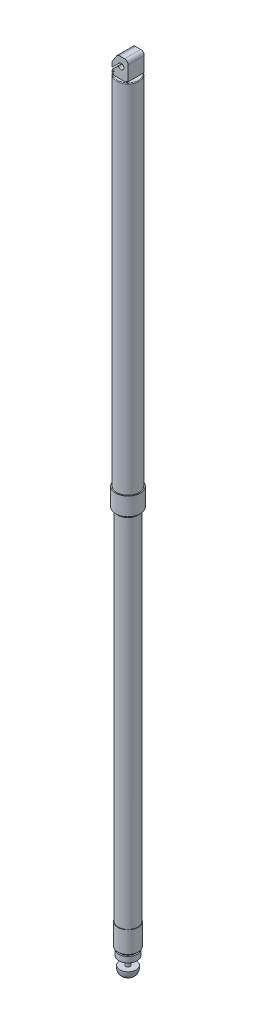
SolidWorks part; units mm, degrees
ref_plane "Front Plane" through (0, 0, 0) normal (0, 0, 1) x (1, 0, 0)
ref_plane "Top Plane" through (0, 0, 0) normal (0, 1, 0) x (1, 0, 0)
ref_plane "Right Plane" through (0, 0, 0) normal (1, 0, 0) x (0, 0, -1)
sketch "Sketch1" plane through (0, 0, 0) normal (0, 0, 1) x (1, 0, 0)
  line L0 (-33.0085, -30.177) -> (-48.0085, -30.177)
  line L1 (-48.0085, -30.177) -> (-56.0085, -42.8656)
  line L2 (-56.0085, -42.8656) -> (-56.0085, -49.4403)
  line L3 (-56.0085, -49.4403) -> (-46.7672, -40.8087)
  line L5 (-46.7672, -43.5454) -> (-56.0085, -52.177)
  line L6 (-56.0085, -52.177) -> (-53.0085, -52.177)
  line L7 (-53.0085, -52.177) -> (-53.0085, -54.177)
  line L8 (-53.0085, -54.177) -> (-56.0085, -54.177)
  line L9 (-56.0085, -54.177) -> (-56.0085, -56.177)
  line L10 (-56.0085, -56.177) -> (-54.0085, -56.177)
  line L11 (-54.0085, -56.177) -> (-54.0085, -58.177)
  line L12 (-54.0085, -58.177) -> (-35.0085, -58.177)
  line L13 (-35.0085, -58.177) -> (-35.0085, -56.177)
  line L14 (-35.0085, -56.177) -> (-33.0085, -56.177)
  line L15 (-33.0085, -56.177) -> (-33.0085, -30.177)
  arc A0 (-46.7672, -43.5454) -> (-46.7672, -40.8087) centre (-43.0085, -42.177) ccw
  dimension "D15" = 4
  dimension "D2" = 28
  dimension "D3" = 2
  dimension "D4" = 2
  dimension "D5" = 2
  dimension "D6" = 2
  dimension "D7" = 2
  dimension "D8" = 15
  dimension "D9" = 15
  dimension "D10" = 2
  dimension "D11" = 3
  dimension "D12" = 19
  dimension "D13" = 12
  dimension "D14" = 10
extrude "Boss-Extrude1" add sketch "Sketch1" along normal mid plane 23
fillet "Fillet1" radius 5 3 edges at (-56.0085, -42.8656, 0) (-48.0085, -30.177, 0) (-33.0085, -30.177, 0)
sketch "Sketch2" plane through (0, -58.177, 0) normal (0, -1, 0) x (-1, 0, 0)
  line L0 (35.0085, -11.5) -> (54.0085, 11.2984) construction
  line L1 (54.0085, -11.5) -> (54.0085, 11.5) construction
  circle A0 centre (44.5085, -0.1008) radius 16
  dimension "D1" = 32
extrude "Boss-Extrude2" add sketch "Sketch2" along normal blind 508
fillet "Fillet2" radius 1 1 edges at (-44.5085, -58.177, -15.8992)
ref_axis "Axis1" through (-44.5085, -566.177, 0.1008) along (0, 1, 0)
sketch "Sketch4" plane through (0, -566.177, 0) normal (0, -1, 0) x (-1, 0, 0)
  circle A0 centre (44.5085, -0.1008) radius 17.5
  dimension "D1" = 35
extrude "Boss-Extrude3" add sketch "Sketch4" along normal blind 29
chamfer "Chamfer1" distance 3.5 angle 45 1 edges at (-44.5085, -595.177, -17.3992)
sketch "Sketch5" plane through (0, -595.177, 0) normal (0, -1, 0) x (-1, 0, 0)
  circle A1 centre (44.5085, -0.1008) radius 14
  circle A2 centre (44.5085, -0.1008) radius 14
  dimension "D1" = 0
extrude "Boss-Extrude4" add sketch "Sketch5" along normal blind 508
sketch "Sketch6" plane through (0, -1103.177, 0) normal (0, -1, 0) x (1, 0, 0)
  circle A0 centre (-44.5085, 0.1008) radius 14.5
  dimension "D1" = 29
extrude "Boss-Extrude5" add sketch "Sketch6" along normal blind 34
chamfer "Chamfer2" distance 3.5 angle 45 1 edges at (-44.5085, -1137.177, -14.3992)
sketch "Sketch7" plane through (0, -1137.177, 0) normal (0, -1, 0) x (1, 0, 0)
  circle A0 centre (-44.5085, 0.1008) radius 13
  circle A1 centre (-44.5085, 0.1008) radius 11 construction
  dimension "D1" = 26
extrude "Boss-Extrude6" add sketch "Sketch7" along normal blind 8
sketch "Sketch8" plane through (0, -1145.177, 0) normal (0, -1, 0) x (1, 0, 0)
  circle A0 centre (-44.5085, 0.1008) radius 3.175
  circle A2 centre (-44.5085, 0.1008) radius 13 construction
  dimension "D1" = 6.35
extrude "Boss-Extrude7" add sketch "Sketch8" along normal blind 12
sketch "Sketch9" plane through (0, -1157.177, 0) normal (0, -1, 0) x (-1, 0, 0)
  circle A0 centre (44.5085, -0.1008) radius 11.5
  circle A1 centre (44.5085, -0.1008) radius 3.175 construction
  point P3 (41.3335, -0.1008)
  dimension "D1" = 23
extrude "Boss-Extrude8" add sketch "Sketch9" along normal blind 12
fillet "Fillet3" radius 9 1 edges at (-44.5085, -1169.177, -11.3992)
